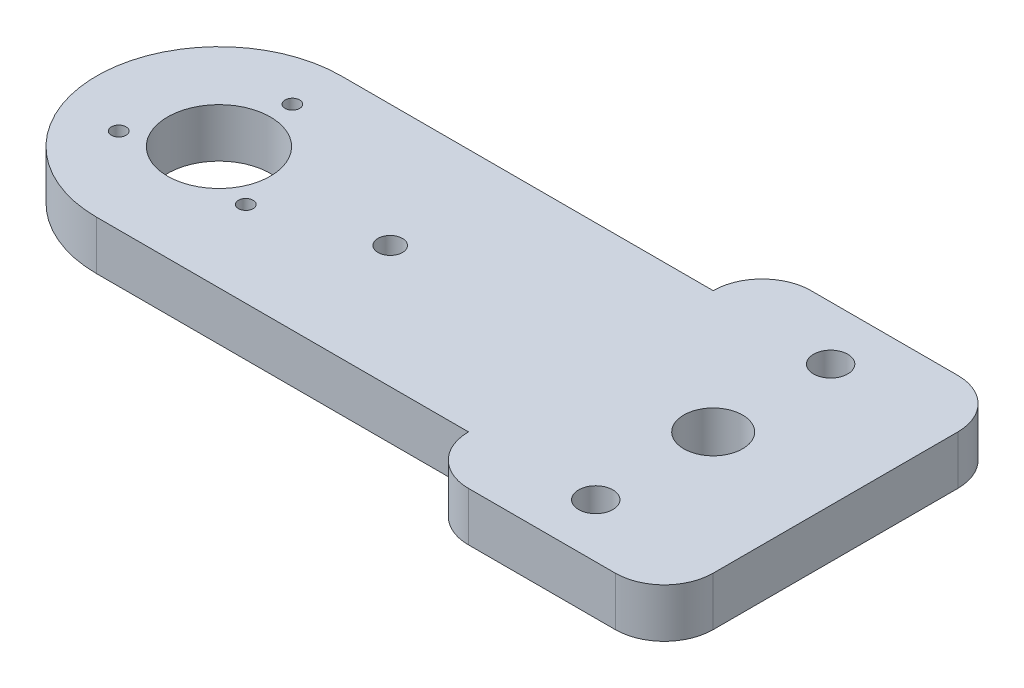
SolidWorks part; units mm, degrees
material "6061 Alloy"
ref_plane "Front Plane" through (0, 0, 0) normal (0, 0, 1) x (1, 0, 0)
ref_plane "Top Plane" through (0, 0, 0) normal (0, 1, 0) x (1, 0, 0)
ref_plane "Right Plane" through (0, 0, 0) normal (1, 0, 0) x (0, 0, -1)
sketch "Sketch1" plane through (0, 0, 0) normal (0, 1, 0) x (1, 0, 0)
  line L0 (0, 0) -> (101, 0) construction
  line L3 (0, 0) -> (0, 25) construction
  line L4 (0, 0) -> (101, 0) construction
  line L5 (76, -35) -> (126, -35)
  line L6 (76, -35) -> (76, 35)
  line L8 (76, 35) -> (126, 35)
  line L9 (126, -35) -> (126, 35)
  line L10 (0, 25) -> (101, 25)
  line L11 (0, -25) -> (101, -25)
  line L12 (0, 15) -> (0, -15)
  line L13 (0, 0) -> (-12.9904, -7.5)
  line L14 (-12.9904, 7.5) -> (12.9904, -7.5)
  circle A2 centre (0, 0) radius 10.5
  circle A9 centre (101, 0) radius 6
  arc A13 (0, 25) -> (0, -25) centre (0, 0) ccw
  circle A14 centre (101, 24) radius 3.5
  circle A15 centre (101, -24) radius 3.5
  arc A16 (101, -25) -> (101, 25) centre (101, 0) ccw
  circle A17 centre (35, 0) radius 2.5
  circle A18 centre (0, 0) radius 15
  circle A19 centre (0, 15) radius 1.5
  circle A20 centre (12.9904, -7.5) radius 1.5
  circle A21 centre (-12.9904, -7.5) radius 1.5
  point P5 (50.5, 0)
  point P28 (0, 0)
  dimension "D2" = 21
  dimension "D3" = 25
  dimension "D4" = 30
  dimension "D5" = 3
  dimension "D9" = 12
  dimension "D12" = 35
  dimension "D14" = 35
  dimension "D16" = 25.9808
  dimension "D18" = 7
  dimension "D11" = 50
  dimension "D13" = 5
  dimension "D8" = 3
  dimension "3" = 3
  dimension "D7" = 120
  dimension "D10" = 70
  dimension "D17" = 24
  dimension "D6" = 120
extrude "Boss-Extrude1" add sketch "Sketch1" along normal blind 10 contours L10 A13 L11 L6 A21 A18 A19 A20 A17 | A19 A18 L14 A2 L12 | A21 L13 A2 L14 A18 | A21 A18 L12 A2 L13 | A20 L14 A2 L12 A18 | A20 A18 A19 L12 A2 L14 | A15 A16 A14 L10 L6 L11 A9 | A16 A15 L11 L6 L5 L9 | A16 L9 L8 L6 L10 A14 region at (105.1889, 0, 27.7967) region at (38, 0, 23.873) region at (76.7071, 0, 0) region at (105.1889, 0, -27.7967) region at (9.3017, 0, -5.3703) region at (-6.3146, 0, -10.5441) region at (-12.2887, 0, -0.1966) region at (5.9741, 0, 10.7407) region at (-5.9741, 0, 10.7407)
fillet "Fillet1" radius 10 1 edges at (126, 5, 35)
fillet "Fillet2" radius 10 1 edges at (76, 5, 35)
fillet "Fillet3" radius 10 1 edges at (76, 5, -35)
fillet "Fillet4" radius 10 1 edges at (126, 5, -35)
